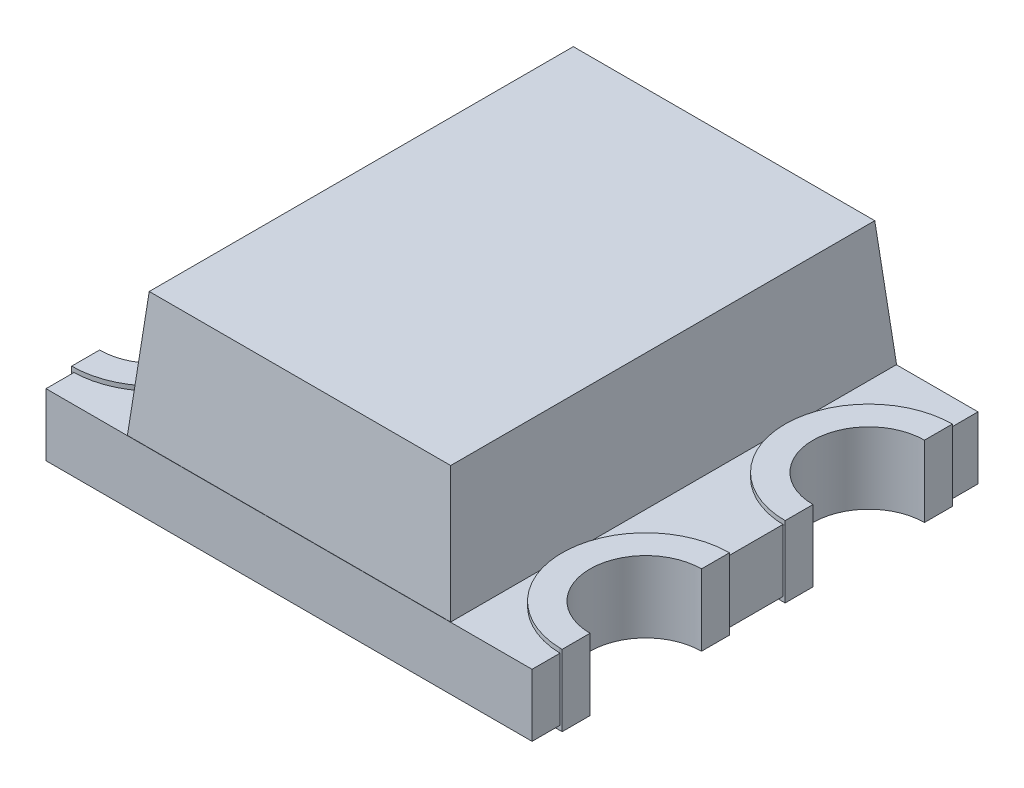
SolidWorks part; units mm, degrees
ref_plane "Front Plane" through (0, 0, 0) normal (0, 0, 1) x (1, 0, 0)
ref_plane "Top Plane" through (0, 0, 0) normal (0, 1, 0) x (1, 0, 0)
ref_plane "Right Plane" through (0, 0, 0) normal (1, 0, 0) x (0, 0, -1)
sketch "Sketch1" plane through (0, 0, 0) normal (0, 1, 0) x (1, 0, 0)
  line L1 (1.1, 1) -> (-1.1, 1)
  line L2 (1.1, 1) -> (1.1, -1)
  line L3 (1.1, -1) -> (-1.1, -1)
  line L4 (-1.1, 1) -> (-1.1, -1)
  line L5 (1.1, 1) -> (-1.1, -1) construction
  line L6 (1.1, -1) -> (-1.1, 1) construction
  point P0 (0, 0)
  dimension "D1" = 2
  dimension "D2" = 2.2
extrude "Boss-Extrude1" add sketch "Sketch1" along normal blind 0.28
sketch "Sketch2" plane through (0, 0.28, 0) normal (0, 1, 0) x (1, 0, 0)
  line L0 (-1.1, 1) -> (-1.1, -1) construction
  line L1 (-1.1, 0.875) -> (-0.565, 0.875)
  line L2 (-1.1, 0.875) -> (-1.1, 0.125)
  line L3 (-1.1, 0.125) -> (-0.565, 0.125)
  line L4 (-0.565, 0.875) -> (-0.565, 0.125)
  line L5 (0, 0) -> (0, 0.3307) construction
  line L6 (0, 0) -> (0.4542, 0) construction
  line L7 (0.565, 0.875) -> (0.565, 0.125)
  line L8 (1.1, 0.125) -> (0.565, 0.125)
  line L9 (1.1, 0.875) -> (1.1, 0.125)
  line L10 (1.1, 0.875) -> (0.565, 0.875)
  line L11 (1.1, -0.875) -> (0.565, -0.875)
  line L12 (1.1, -0.875) -> (1.1, -0.125)
  line L13 (1.1, -0.125) -> (0.565, -0.125)
  line L14 (0.565, -0.875) -> (0.565, -0.125)
  line L15 (-0.565, -0.875) -> (-0.565, -0.125)
  line L16 (-1.1, -0.125) -> (-0.565, -0.125)
  line L17 (-1.1, -0.875) -> (-1.1, -0.125)
  line L18 (-1.1, -0.875) -> (-0.565, -0.875)
  circle A0 centre (-1.1, 0.5) radius 0.25
  circle A1 centre (1.1, 0.5) radius 0.25
  circle A2 centre (1.1, -0.5) radius 0.25
  circle A3 centre (-1.1, -0.5) radius 0.25
  point P9 (-0.565, 0.5)
  line M5 (-1.1, 1) -> (-1.1, -1)
  line M7 (1.1, -1) -> (1.1, 1)
  dimension "D3" = 0.535
  dimension "D4" = 0.5
  dimension "D1" = 0.5
  dimension "D2" = 0.75
extrude "Boss-Extrude2" add sketch "Sketch2" along normal blind 0.02 contours A0 L3 L4 L1 M5 | A1 L10 L7 L8 M7 | A2 L13 L14 L11 M7 | A3 L18 L15 L16 M5 region at (-0.7802, 0.28, 0.5) region at (-0.7802, 0.28, -0.5) region at (0.7802, 0.28, -0.5) region at (0.7802, 0.28, 0.5)
sketch "Sketch3" plane through (0, 0.28, 0) normal (0, 1, 0) x (1, 0, 0)
  line L1 (-1.1, 0.75) -> (-1.1, 0.25)
  line L2 (-1.1, 0.75) -> (-1.1, 0.25)
  line L3 (-1.1, -0.25) -> (-1.1, -0.75)
  line L4 (-1.1, -0.25) -> (-1.1, -0.75)
  line L5 (1.1, 0.25) -> (1.1, 0.75)
  line L6 (1.1, 0.25) -> (1.1, 0.75)
  line L7 (1.1, -0.75) -> (1.1, -0.25)
  line L8 (1.1, -0.75) -> (1.1, -0.25)
  arc A1 (-1.1, 0.25) -> (-1.1, 0.75) centre (-1.1, 0.5) ccw
  arc A2 (-1.1, 0.25) -> (-1.1, 0.75) centre (-1.1, 0.5) ccw
  arc A3 (-1.1, -0.75) -> (-1.1, -0.25) centre (-1.1, -0.5) ccw
  arc A4 (-1.1, -0.75) -> (-1.1, -0.25) centre (-1.1, -0.5) ccw
  arc A5 (1.1, 0.75) -> (1.1, 0.25) centre (1.1, 0.5) ccw
  arc A6 (1.1, 0.75) -> (1.1, 0.25) centre (1.1, 0.5) ccw
  arc A7 (1.1, -0.25) -> (1.1, -0.75) centre (1.1, -0.5) ccw
  arc A8 (1.1, -0.25) -> (1.1, -0.75) centre (1.1, -0.5) ccw
  dimension "D1" = 0
  dimension "D2" = 0
  dimension "D3" = 0
  dimension "D4" = 0
extrude "Cut-Extrude1" cut sketch "Sketch3" against normal blind 2
sketch "Sketch4" plane through (-1.1, 0, 0) normal (-1, 0, 0) x (0, 0, 1)
  line L0 (-0.875, 0.28) -> (-0.875, 0)
  line L1 (-1, 0) -> (-0.75, 0) construction
  line L2 (-0.125, 0.28) -> (-0.125, 0)
  line L3 (-0.25, 0) -> (0.25, 0) construction
  line L4 (0.125, 0.28) -> (0.125, 0)
  line L5 (-0.125, 0.28) -> (0.125, 0.28) construction
  line L6 (0.875, 0.28) -> (0.875, 0)
  line L7 (0.75, 0) -> (1, 0) construction
  line L14 (-1, 0) -> (-0.75, 0)
  line L15 (-0.75, 0) -> (-0.75, 0.3)
  line L16 (-0.25, 0) -> (0.25, 0)
  line L17 (0.25, 0) -> (0.25, 0.3)
  line L18 (0.25, 0.3) -> (0.125, 0.3)
  line L19 (0.125, 0.3) -> (0.125, 0.28)
  line L20 (0.125, 0.28) -> (-0.125, 0.28)
  line L21 (-0.125, 0.28) -> (-0.125, 0.3)
  line L22 (-0.125, 0.3) -> (-0.25, 0.3)
  line L23 (-0.25, 0.3) -> (-0.25, 0)
  line L24 (-0.25, 0) -> (0.25, 0)
  line L25 (0.25, 0) -> (0.25, 0.3)
  line L26 (0.25, 0.3) -> (0.125, 0.3)
  line L27 (0.125, 0.3) -> (0.125, 0.28)
  line L28 (0.125, 0.28) -> (-0.125, 0.28)
  line L29 (-0.125, 0.28) -> (-0.125, 0.3)
  line L30 (-0.125, 0.3) -> (-0.25, 0.3)
  line L31 (-0.25, 0.3) -> (-0.25, 0)
  line L32 (-0.75, 0.3) -> (-0.875, 0.3)
  line L33 (-0.875, 0.3) -> (-0.875, 0.28)
  line L34 (-0.875, 0.28) -> (-1, 0.28)
  line L35 (-1, 0.28) -> (-1, 0)
  line L36 (-1, 0) -> (-0.75, 0)
  line L37 (-0.75, 0) -> (-0.75, 0.3)
  line L38 (-0.75, 0.3) -> (-0.875, 0.3)
  line L39 (-0.875, 0.3) -> (-0.875, 0.28)
  line L40 (-0.875, 0.28) -> (-1, 0.28)
  line L41 (-1, 0.28) -> (-1, 0)
  line L42 (0.75, 0.3) -> (0.75, 0)
  line L43 (0.75, 0) -> (1, 0)
  line L44 (1, 0) -> (1, 0.28)
  line L45 (1, 0.28) -> (0.875, 0.28)
  line L46 (0.875, 0.28) -> (0.875, 0.3)
  line L47 (0.875, 0.3) -> (0.75, 0.3)
  line L48 (0.75, 0.3) -> (0.75, 0)
  line L49 (0.75, 0) -> (1, 0)
  line L50 (1, 0) -> (1, 0.28)
  line L51 (1, 0.28) -> (0.875, 0.28)
  line L52 (0.875, 0.28) -> (0.875, 0.3)
  line L53 (0.875, 0.3) -> (0.75, 0.3)
  line M21 (-1, 0) -> (-0.75, 0)
  line M25 (-0.875, 0.28) -> (-1, 0.28)
  line M26 (-1, 0.28) -> (-1, 0)
  dimension "D1" = 0
  dimension "D2" = 0
  dimension "D3" = 0
extrude "Cut-Extrude2" cut sketch "Sketch4" against normal blind 0.01 contours L0 M25 M26 M21 | L4 L28 L2 L24 | L50 L51 L6 L49 region at (-1.1, 0.14, -0.9375) region at (-1.1, 0.14, 0) region at (-1.1, 0.14, 0.9375)
sketch "Sketch5" plane through (1.1, 0, 0) normal (1, 0, 0) x (0, 0, -1)
  line L0 (-0.875, 0.28) -> (-0.875, 0)
  line L1 (-1, 0) -> (-0.75, 0) construction
  line L2 (-0.125, 0.28) -> (-0.125, 0)
  line L3 (-0.25, 0) -> (0.25, 0) construction
  line L4 (0.125, 0.28) -> (0.125, 0)
  line L5 (0.875, 0.28) -> (0.875, 0)
  line L6 (0.75, 0) -> (1, 0) construction
  line L13 (-1, 0) -> (-0.75, 0)
  line L14 (-0.75, 0) -> (-0.75, 0.3)
  line L15 (-0.75, 0.3) -> (-0.875, 0.3)
  line L16 (-0.875, 0.3) -> (-0.875, 0.28)
  line L17 (-0.875, 0.28) -> (-1, 0.28)
  line L18 (-1, 0.28) -> (-1, 0)
  line L19 (-1, 0) -> (-0.75, 0)
  line L20 (-0.75, 0) -> (-0.75, 0.3)
  line L21 (-0.75, 0.3) -> (-0.875, 0.3)
  line L22 (-0.875, 0.3) -> (-0.875, 0.28)
  line L23 (-0.875, 0.28) -> (-1, 0.28)
  line L24 (-1, 0.28) -> (-1, 0)
  line L25 (0.75, 0.3) -> (0.75, 0)
  line L26 (0.75, 0) -> (1, 0)
  line L27 (-0.25, 0) -> (0.25, 0)
  line L28 (0.25, 0) -> (0.25, 0.3)
  line L29 (0.25, 0.3) -> (0.125, 0.3)
  line L30 (0.125, 0.3) -> (0.125, 0.28)
  line L31 (0.125, 0.28) -> (-0.125, 0.28)
  line L32 (-0.125, 0.28) -> (-0.125, 0.3)
  line L33 (-0.125, 0.3) -> (-0.25, 0.3)
  line L34 (-0.25, 0.3) -> (-0.25, 0)
  line L35 (-0.25, 0) -> (0.25, 0)
  line L36 (0.25, 0) -> (0.25, 0.3)
  line L37 (0.25, 0.3) -> (0.125, 0.3)
  line L38 (0.125, 0.3) -> (0.125, 0.28)
  line L39 (0.125, 0.28) -> (-0.125, 0.28)
  line L40 (-0.125, 0.28) -> (-0.125, 0.3)
  line L41 (-0.125, 0.3) -> (-0.25, 0.3)
  line L42 (-0.25, 0.3) -> (-0.25, 0)
  line L43 (1, 0) -> (1, 0.28)
  line L44 (1, 0.28) -> (0.875, 0.28)
  line L45 (0.875, 0.28) -> (0.875, 0.3)
  line L46 (0.875, 0.3) -> (0.75, 0.3)
  line L47 (0.75, 0.3) -> (0.75, 0)
  line L48 (0.75, 0) -> (1, 0)
  line L49 (1, 0) -> (1, 0.28)
  line L50 (1, 0.28) -> (0.875, 0.28)
  line L51 (0.875, 0.28) -> (0.875, 0.3)
  line L52 (0.875, 0.3) -> (0.75, 0.3)
  line M21 (-0.25, 0) -> (0.25, 0)
  line M25 (0.125, 0.28) -> (-0.125, 0.28)
  dimension "D1" = 0
  dimension "D2" = 0
  dimension "D3" = 0
extrude "Cut-Extrude3" cut sketch "Sketch5" against normal blind 0.01 contours L23 L24 L19 L0 | L4 L2 M25 M21 | L49 L50 L5 L48 region at (1.1, 0.14, 0.9375) region at (1.1, 0.14, 0) region at (1.1, 0.14, -0.9375)
sketch "Sketch6" plane through (0, 0, 0) normal (0, -1, 0) x (1, 0, 0)
  line L0 (-1.09, 1) -> (1.09, 1) construction
  line L1 (-0.725, 1) -> (0.725, 1)
  line L2 (-0.725, 1) -> (-0.725, -1)
  line L3 (-0.725, -1) -> (0.725, -1)
  line L4 (0.725, 1) -> (0.725, -1)
  line L5 (1.09, -1) -> (-1.09, -1) construction
  dimension "D1" = 1.45
  dimension "D2" = 0.725
extrude "Boss-Extrude3" add sketch "Sketch6" along normal blind 0.56 draft 5
sketch "Sketch8" plane through (0, 0, 0) normal (0, -1, 0) x (1, 0, 0)
  line L1 (-0.725, 1) -> (0.725, 1)
  line L2 (-0.725, 1) -> (-0.725, -1)
  line L3 (-0.725, -1) -> (0.725, -1)
  line L4 (0.725, 1) -> (0.725, -1)
extrude "Cut-Extrude4" cut sketch "Sketch8" along normal blind 0.001
sketch "Sketch10" plane through (0, 0, 0) normal (0, -1, 0) x (1, 0, 0)
  line L0 (-1.09, 1) -> (1.09, 1) construction
  line L1 (-0.3, -0.04) -> (0.39, -0.04)
  line L2 (-0.3, -0.04) -> (-0.3, 0.5)
  line L3 (-0.3, 0.5) -> (0.39, 0.5)
  line L4 (0.39, -0.04) -> (0.39, 0.5)
  line L5 (-1.1, 0.125) -> (-1.1, 0.25) construction
  dimension "D1" = 0.5
  dimension "D2" = 0.54
  dimension "D3" = 0.69
  dimension "D4" = 0.8
extrude "Boss-Extrude5" [suppressed] add sketch "Sketch10" along normal blind 0.2
sketch "Sketch11" [suppressed] plane through (0, -0.001, 0) normal (0, 1, 0) x (1, 0, 0)
  line L0 (-0.3, -0.5) -> (-0.3, 0.04) construction
  line L1 (-0.3, -0.5) -> (0.39, -0.5)
  line L2 (-0.3, -0.5) -> (-0.3, 0.04)
  line L3 (-0.3, 0.04) -> (0.39, 0.04)
  line L4 (0.39, -0.5) -> (0.39, 0.04)
  line L5 (0.39, -0.5) -> (-0.3, -0.5) construction
  line L6 (-0.31, -0.51) -> (-0.31, 0.05)
  line L7 (-0.31, 0.05) -> (0.4, 0.05)
  line L8 (0.4, -0.51) -> (0.4, 0.05)
  line L9 (-0.31, -0.51) -> (0.4, -0.51)
  line M5 (0.39, -0.5) -> (-0.3, -0.5)
  line M6 (-0.3, -0.5) -> (-0.3, 0.04)
  line M7 (-0.3, 0.04) -> (0.39, 0.04)
  line M8 (0.39, 0.04) -> (0.39, -0.5)
  dimension "D1" = 0.01
extrude "Cut-Extrude5" [suppressed] cut sketch "Sketch11" against normal blind 0.201 contours M5 M8 M7 M6 | L6 L9 L8 L7 M8 M5 M6 M7
sketch "Sketch9" plane through (0, 0, 0) normal (0, -1, 0) x (1, 0, 0)
  line L24 (-1.09, -0.875) -> (-1.09, -1)
  line L25 (-1.09, -1) -> (1.09, -1)
  line L26 (1.09, -1) -> (1.09, -0.875)
  line L27 (1.09, -0.875) -> (1.1, -0.875)
  line L28 (1.1, -0.875) -> (1.1, -0.75)
  line L29 (1.1, -0.25) -> (1.1, -0.125)
  line L30 (1.1, -0.125) -> (1.09, -0.125)
  line L31 (1.09, -0.125) -> (1.09, 0.125)
  line L32 (1.09, 0.125) -> (1.1, 0.125)
  line L33 (1.1, 0.125) -> (1.1, 0.25)
  line L34 (1.1, 0.75) -> (1.1, 0.875)
  line L35 (1.1, 0.875) -> (1.09, 0.875)
  line L36 (1.09, 0.875) -> (1.09, 1)
  line L37 (1.09, 1) -> (-1.09, 1)
  line L38 (-1.09, 1) -> (-1.09, 0.875)
  line L39 (-1.09, 0.875) -> (-1.1, 0.875)
  line L40 (-1.1, 0.875) -> (-1.1, 0.75)
  line L41 (-1.1, 0.25) -> (-1.1, 0.125)
  line L42 (-1.1, 0.125) -> (-1.09, 0.125)
  line L43 (-1.09, 0.125) -> (-1.09, -0.125)
  line L44 (-1.09, -0.125) -> (-1.1, -0.125)
  line L45 (-1.1, -0.125) -> (-1.1, -0.25)
  line L46 (-1.1, -0.75) -> (-1.1, -0.875)
  line L47 (-1.1, -0.875) -> (-1.09, -0.875)
  line L48 (-1.09, -0.875) -> (-1.09, -1)
  line L49 (-1.09, -1) -> (1.09, -1)
  line L50 (1.09, -1) -> (1.09, -0.875)
  line L51 (1.09, -0.875) -> (1.1, -0.875)
  line L52 (1.1, -0.875) -> (1.1, -0.75)
  line L53 (1.1, -0.25) -> (1.1, -0.125)
  line L54 (1.1, -0.125) -> (1.09, -0.125)
  line L55 (1.09, -0.125) -> (1.09, 0.125)
  line L56 (1.09, 0.125) -> (1.1, 0.125)
  line L57 (1.1, 0.125) -> (1.1, 0.25)
  line L58 (1.1, 0.75) -> (1.1, 0.875)
  line L59 (1.1, 0.875) -> (1.09, 0.875)
  line L60 (1.09, 0.875) -> (1.09, 1)
  line L61 (1.09, 1) -> (-1.09, 1)
  line L62 (-1.09, 1) -> (-1.09, 0.875)
  line L63 (-1.09, 0.875) -> (-1.1, 0.875)
  line L64 (-1.1, 0.875) -> (-1.1, 0.75)
  line L65 (-1.1, 0.25) -> (-1.1, 0.125)
  line L66 (-1.1, 0.125) -> (-1.09, 0.125)
  line L67 (-1.09, 0.125) -> (-1.09, -0.125)
  line L68 (-1.09, -0.125) -> (-1.1, -0.125)
  line L69 (-1.1, -0.125) -> (-1.1, -0.25)
  line L70 (-1.1, -0.75) -> (-1.1, -0.875)
  line L71 (-1.1, -0.875) -> (-1.09, -0.875)
  arc A0 (-1.1, 0.125) -> (-1.1, 0.875) centre (-1.1, 0.5) ccw
  arc A1 (-1.1, -0.875) -> (-1.1, -0.125) centre (-1.1, -0.5) ccw
  arc A2 (1.1, 0.875) -> (1.1, 0.125) centre (1.1, 0.5) ccw
  arc A3 (1.09, -0.125) -> (1.09, -0.875) centre (1.1, -0.5) ccw
  arc A8 (1.1, -0.25) -> (1.1, -0.75) centre (1.1, -0.5) ccw
  arc A9 (1.1, 0.75) -> (1.1, 0.25) centre (1.1, 0.5) ccw
  arc A10 (-1.1, 0.25) -> (-1.1, 0.75) centre (-1.1, 0.5) ccw
  arc A11 (-1.1, -0.75) -> (-1.1, -0.25) centre (-1.1, -0.5) ccw
  arc A12 (1.1, -0.25) -> (1.1, -0.75) centre (1.1, -0.5) ccw
  arc A13 (1.1, 0.75) -> (1.1, 0.25) centre (1.1, 0.5) ccw
  arc A14 (-1.1, 0.25) -> (-1.1, 0.75) centre (-1.1, 0.5) ccw
  arc A15 (-1.1, -0.75) -> (-1.1, -0.25) centre (-1.1, -0.5) ccw
  line M33 (1.09, -0.875) -> (1.1, -0.875)
  line M34 (1.1, -0.875) -> (1.1, -0.75)
  arc M35 (1.1, -0.75) -> (1.1, -0.25) centre (1.1, -0.5) cw
  line M36 (1.1, -0.25) -> (1.1, -0.125)
  line M37 (1.1, -0.125) -> (1.09, -0.125)
  line M40 (1.1, 0.125) -> (1.1, 0.25)
  arc M41 (1.1, 0.25) -> (1.1, 0.75) centre (1.1, 0.5) cw
  line M42 (1.1, 0.75) -> (1.1, 0.875)
  line M48 (-1.1, 0.875) -> (-1.1, 0.75)
  arc M49 (-1.1, 0.75) -> (-1.1, 0.25) centre (-1.1, 0.5) cw
  line M50 (-1.1, 0.25) -> (-1.1, 0.125)
  line M54 (-1.1, -0.125) -> (-1.1, -0.25)
  arc M55 (-1.1, -0.25) -> (-1.1, -0.75) centre (-1.1, -0.5) cw
  line M56 (-1.1, -0.75) -> (-1.1, -0.875)
  dimension "D2" = 0
extrude "Boss-Extrude4" add sketch "Sketch9" along normal blind 0.02 contours A0 M50 M48 M49 | A1 M56 M54 M55 | A2 M42 M40 M41 | A3 M37 M33 M34 M35 M36 region at (-1.0916, 0, -0.8125) region at (0.7333, 0, -0.5) region at (-1.0916, 0, 0.1875) region at (0.7334, 0, 0.5)
sketch "Sketch12" plane through (0, 0.28, 0) normal (0, 1, 0) x (1, 0, 0)
  line L0 (0.315, 0.675) -> (0.315, -0.675) construction
  line L1 (0.515, 0.675) -> (0.515, -0.675)
  line L2 (0.115, 0.675) -> (0.115, -0.675)
  line L3 (0.565, 0.875) -> (0.565, 0.125) construction
  line L4 (1.09, 0.875) -> (0.565, 0.875) construction
  arc A0 (0.515, 0.675) -> (0.115, 0.675) centre (0.315, 0.675) ccw
  arc A1 (0.115, -0.675) -> (0.515, -0.675) centre (0.315, -0.675) ccw
  point P2 (0.315, 0)
  dimension "D1" = 0.25
  dimension "D2" = 0
  dimension "D3" = 0.2
extrude "Boss-Extrude6" add sketch "Sketch12" along normal blind 0.02
move or copy body "Body-Move/Copy1" bodies to move or copy 113 copy no rotation origin (0, 0, 0) rotation axis (-1, 0, 0) rotation angle 90
move or copy body "Body-Move/Copy2" bodies to move or copy 114 copy no translate (0, 0, 0.3)
move or copy body "Body-Move/Copy3" bodies to move or copy 115 copy no rotation origin (0, 0, 0) rotation axis (-1, 0, 0) rotation angle 90
